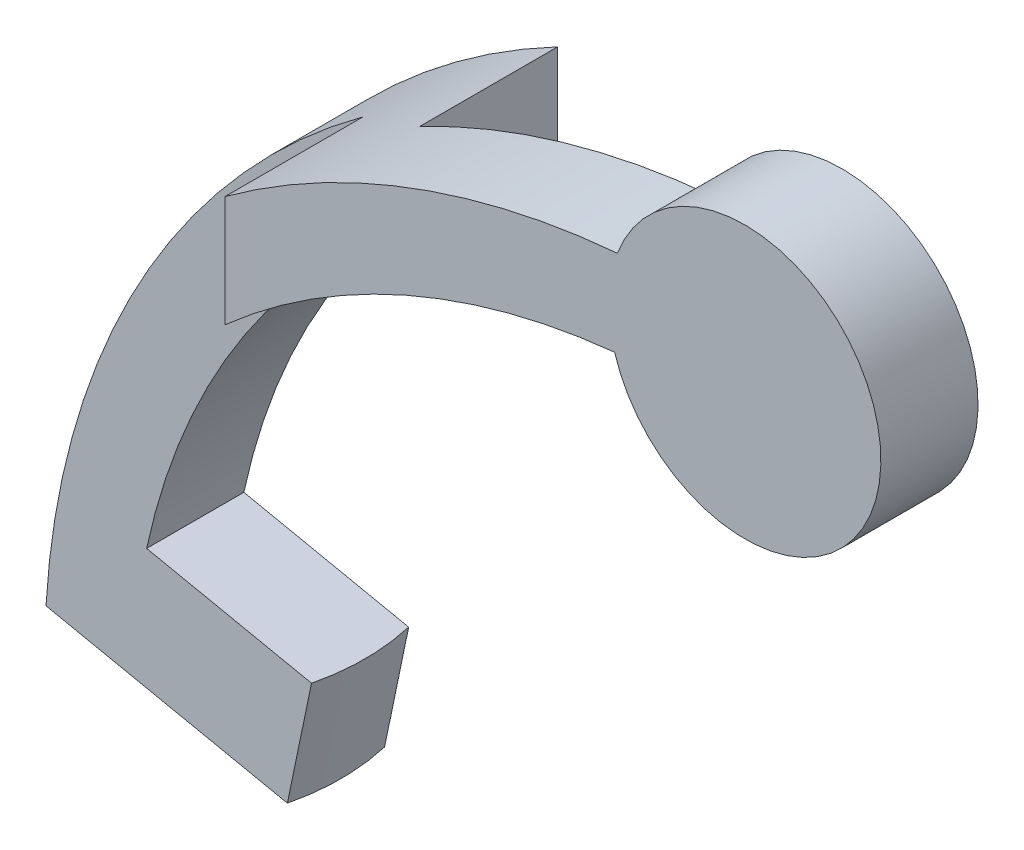
SolidWorks part; units mm, degrees
ref_plane "Front Plane" through (0, 0, 0) normal (0, 0, 1) x (1, 0, 0)
ref_plane "Top Plane" through (0, 0, 0) normal (0, 1, 0) x (1, 0, 0)
ref_plane "Right Plane" through (0, 0, 0) normal (1, 0, 0) x (0, 0, -1)
sketch "Esquisse3" plane through (0, 0, 0) normal (0, 0, 1) x (1, 0, 0)
  line L0 (-43.0597, -35.0596) -> (-29.6704, -37.8465)
  line L1 (-29.6704, -37.8465) -> (-28.4288, -31.8813)
  line L2 (-28.4288, -31.8813) -> (-37.881, -29.9139)
  circle A0 centre (0, 0) radius 7
  arc A1 (-6.5562, 2.4527) -> (-43.0597, -35.0596) centre (-3.1282, -37.4001) ccw
  arc A2 (-37.881, -29.9139) -> (-6.6992, -2.0301) centre (-3.1282, -37.4001) cw
  dimension "D1" = 14
  dimension "D2" = 40
extrude "Boss.-Extru.2" add sketch "Esquisse3" along normal blind 5 contours A0 region at (0, 0, 0)
extrude "Boss.-Extru.3" add sketch "Esquisse3<3>" along normal blind 45 contours L2 A2 A0 A1 L0 L1 region at (-31.4057, -9.8832, 0)
sketch "Esquisse3<3>" plane through (0, 0, 0) normal (0, 0, 1) x (1, 0, 0) same geometry as "Esquisse3"
sketch "Esquisse4" plane through (0, 0, 0) normal (0, 1, 0) x (1, 0, 0)
  line L0 (-6.5562, 0) -> (-6.5562, -5)
  line L4 (-6.5562, -5) -> (-6.5562, 0) construction
  line L6 (-6.5562, -45) -> (-6.5562, -5) construction
  line L8 (-6.5562, -21.6438) -> (-6.5562, -5)
  line L10 (-43.0597, -11.9185) -> (-43.0597, -53.527)
  line L11 (-43.0597, -53.527) -> (-6.4252, -53.527)
  line L12 (-6.4252, -53.527) -> (-6.5562, -21.6438)
  line L13 (-43.0597, -11.9185) -> (-43.0597, -12.1041)
  line L14 (-43.0597, -45) -> (-43.0597, 0) construction
  line L15 (-6.5562, 0) -> (-43.0597, 0) construction
  line L16 (-43.0597, -45) -> (-43.0597, 0)
  line L17 (-6.5562, 0) -> (-43.0597, 0)
  line L18 (-26.7522, 0) -> (-26.7522, -7.1041)
  line L19 (-26.7522, -7.1041) -> (-43.0597, -7.1041)
  line L20 (-43.0597, -7.1041) -> (-43.0597, -12.1041)
  line L21 (-43.0597, -12.1041) -> (-21.7362, -12.1041)
  line L22 (-21.7362, -12.1041) -> (-21.7362, -5)
  line L23 (-21.7362, -5) -> (-6.5562, -5)
  point P4 (-6.5562, -5.2043)
  dimension "D1" = 5
  dimension "D2" = 5
extrude "Enlèv. mat.-Extru.3" cut sketch "Esquisse4" against normal through all and the other way blind 5 contours L8 region at (-24.0756, 0, 31.2154)
extrude "Enlèv. mat.-Extru.4" cut sketch "Esquisse4<4>" against normal through all contours L19 L18 L17 L16 region at (-34.906, 0, 3.552)
sketch "Esquisse4<4>" plane through (0, 0, 0) normal (0, 1, 0) x (1, 0, 0) same geometry as "Esquisse4"
sketch "Esquisse5" plane through (-7.5408, -36.229, 0) normal (0.2038, 0.979, 0) x (0.979, -0.2038, 0)
  line L0 (-30.9904, -7.1041) -> (-21.3357, -7.1041) construction
  line L1 (-22.3267, -7.1041) -> (-21.3357, -7.1041)
  line L2 (-21.3357, -7.1041) -> (-21.3357, -12.1041)
  line L4 (-21.3357, -12.1041) -> (-22.3267, -12.1041)
  line L5 (-30.9904, -12.1041) -> (-21.3357, -12.1041) construction
  arc A2 (-22.3267, -12.1041) -> (-22.3267, -7.1041) centre (-34.8375, -9.6041) ccw
extrude "Enlèv. mat.-Extru.6" cut sketch "Esquisse5" against normal through all
ref_plane "Plan1" through (0, 0, 2.5) normal (0, 0, 1) x (1, 0, 0)
mirror "Symétrie1" about plane through (0, 0, 2.5) normal (0, 0, 1) of "Enlèv. mat.-Extru.3", "Enlèv. mat.-Extru.4", "Boss.-Extru.3", "Enlèv. mat.-Extru.6"
sketch "Esquisse6" plane through (0, 0, 0) normal (0, 1, 0) x (1, 0, 0)
  line L0 (-21.7362, -5) -> (-29.7044, -5)
  line L1 (-21.7362, -12.1041) -> (-21.7362, -5) construction
  line L2 (-43.0597, -12.1041) -> (-21.7362, -12.1041) construction
  line L3 (-43.0597, -12.1041) -> (-43.0597, -7.1041) construction
  line L5 (-21.7362, -12.1041) -> (-21.7362, -5)
  line L6 (-43.0597, -12.1041) -> (-21.7362, -12.1041)
  line L7 (-43.0597, -12.1041) -> (-43.0597, -7.1041)
  line L9 (-43.0597, -7.1041) -> (-29.7044, -5)
extrude "Enlèv. mat.-Extru.7" cut sketch "Esquisse6" against normal through all
